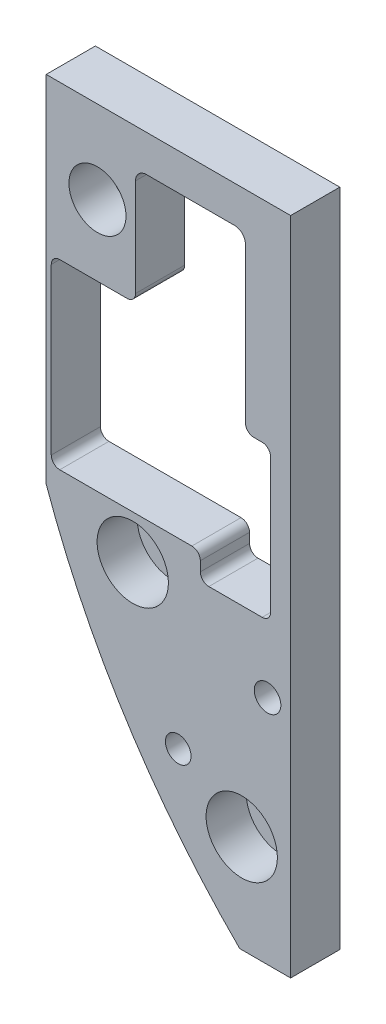
SolidWorks part; units mm, degrees
material "PET"
ref_plane "Front" through (0, 0, 0) normal (0, 0, 1) x (1, 0, 0)
ref_plane "Top" through (0, 0, 0) normal (0, 1, 0) x (1, 0, 0)
ref_plane "Right" through (0, 0, 0) normal (1, 0, 0) x (0, 0, -1)
sketch "Sketch1" plane through (0, 0, 0) normal (0, 0, 1) x (1, 0, 0)
  line L4 (0, -17.78) -> (-45.72, -17.78)
  line L5 (-45.72, -17.78) -> (-45.72, -84.1375)
  line L6 (-9.525, -141.2875) -> (0, -141.2875)
  line L7 (0, -141.2875) -> (0, -17.78)
  line L8 (0, -17.78) -> (-45.72, -17.78)
  line L9 (-45.72, -17.78) -> (-45.72, -84.1375)
  line L10 (-9.525, -141.2875) -> (0, -141.2875)
  line L11 (0, -141.2875) -> (0, -17.78)
  line L17 (-30.5943, -46.5015) -> (-43.1857, -46.5015)
  line L18 (-44.7732, -48.089) -> (-44.7732, -78.9652)
  line L19 (-43.1857, -80.5527) -> (-18.4742, -80.5527)
  line L20 (-16.8867, -82.1402) -> (-16.8867, -83.9371)
  line L21 (-15.2992, -85.5246) -> (-5.3275, -85.5246)
  line L22 (-3.74, -83.9371) -> (-3.74, -58.7502)
  line L23 (-6.8707, -57.1627) -> (-5.3275, -57.1627)
  line L80 (-8.4582, -55.1307) -> (-8.4582, -26.6573)
  line L81 (-26.9748, -57.1627) -> (-10.4902, -57.1627)
  line L82 (-29.0068, -26.6573) -> (-29.0068, -55.1307)
  line L83 (-10.4902, -24.6253) -> (-26.9748, -24.6253)
  line L84 (-8.4582, -55.5752) -> (-8.4582, -26.6573)
  line L86 (-29.0068, -26.6573) -> (-29.0068, -44.914)
  line L87 (-10.4902, -24.6253) -> (-26.9748, -24.6253)
  circle A1 centre (-36.1315, -33.274) radius 2.1526
  circle A2 centre (-36.1315, -33.274) radius 2.1527
  circle A3 centre (-29.5275, -88.7095) radius 2.1526
  circle A4 centre (-29.5275, -88.7095) radius 2.1527
  circle A5 centre (-9.144, -122.9995) radius 2.1526
  circle A6 centre (-9.144, -122.9995) radius 2.1527
  arc A7 (-45.72, -84.1375) -> (-9.525, -141.2875) centre (97.9169, -33.2042) ccw
  arc A8 (-45.72, -84.1375) -> (-9.525, -141.2875) centre (97.9169, -33.2042) ccw
  arc A9 (-3.74, -58.7502) -> (-5.3275, -57.1627) centre (-5.3275, -58.7502) ccw
  arc A10 (-8.4582, -55.5752) -> (-6.8707, -57.1627) centre (-6.8707, -55.5752) ccw
  arc A11 (-30.5943, -46.5015) -> (-29.0068, -44.914) centre (-30.5943, -44.914) ccw
  arc A12 (-43.1857, -46.5015) -> (-44.7732, -48.089) centre (-43.1857, -48.089) ccw
  arc A13 (-44.7732, -78.9652) -> (-43.1857, -80.5527) centre (-43.1857, -78.9652) ccw
  arc A14 (-18.4742, -80.5527) -> (-16.8867, -82.1402) centre (-18.4742, -82.1402) cw
  arc A15 (-16.8867, -83.9371) -> (-15.2992, -85.5246) centre (-15.2992, -83.9371) ccw
  arc A16 (-8.4582, -26.6573) -> (-10.4902, -24.6253) centre (-10.4902, -26.6573) ccw
  arc A17 (-10.4902, -57.1627) -> (-8.4582, -55.1307) centre (-10.4902, -55.1307) ccw
  arc A18 (-29.0068, -55.1307) -> (-26.9748, -57.1627) centre (-26.9748, -55.1307) ccw
  arc A19 (-26.9748, -24.6253) -> (-29.0068, -26.6573) centre (-26.9748, -26.6573) ccw
  arc A20 (-8.4582, -26.6573) -> (-10.4902, -24.6253) centre (-10.4902, -26.6573) ccw
  arc A23 (-26.9748, -24.6253) -> (-29.0068, -26.6573) centre (-26.9748, -26.6573) ccw
  arc A24 (-5.3275, -85.5246) -> (-3.74, -83.9371) centre (-5.3275, -83.9371) ccw
  circle A25 centre (-4.3174, -98.0359) radius 2.487
  circle A26 centre (-21.0247, -114.6804) radius 2.3945
  dimension "D5" = 1.5875
  dimension "D1" = 0
  dimension "D2" = 0
  dimension "D3" = 0
  dimension "D4" = 0
  dimension "D9" = 1.27
extrude "Boss-Extrude1" add sketch "Sketch1" along normal blind 10.8
sketch "Sketch3" plane through (0, 0, 10.8) normal (0, 0, 1) x (1, 0, 0)
  circle A0 centre (-9.144, -122.9995) radius 6.6675
  circle A1 centre (-29.5275, -88.7095) radius 6.6675
  circle A3 centre (-36.1315, -33.274) radius 5.334
  dimension "D1" = 10.668
  dimension "D2" = 13.335
  dimension "D3" = 13.335
extrude "Cut-Extrude1" cut sketch "Sketch3" against normal blind 7.5
sketch "Sketch4" plane through (0, 0, 0) normal (0, 0, -1) x (-1, 0, 0)
  line L4 (0, -17.78) -> (0, -141.2875)
  line L5 (0, -141.2875) -> (9.525, -141.2875)
  line L6 (45.72, -84.1375) -> (45.72, -17.78)
  line L7 (45.72, -17.78) -> (0, -17.78)
  line L8 (0, -17.78) -> (0, -141.2875)
  line L9 (0, -141.2875) -> (9.525, -141.2875)
  line L10 (45.72, -84.1375) -> (45.72, -17.78)
  line L11 (45.72, -17.78) -> (0, -17.78)
  arc A1 (9.525, -141.2875) -> (45.72, -84.1375) centre (-97.9169, -33.2042) ccw
  arc A2 (9.525, -141.2875) -> (45.72, -84.1375) centre (-97.9169, -33.2042) ccw
  dimension "D1" = 0
extrude "Cut-Extrude2" cut sketch "Sketch4" against normal blind 1.6
